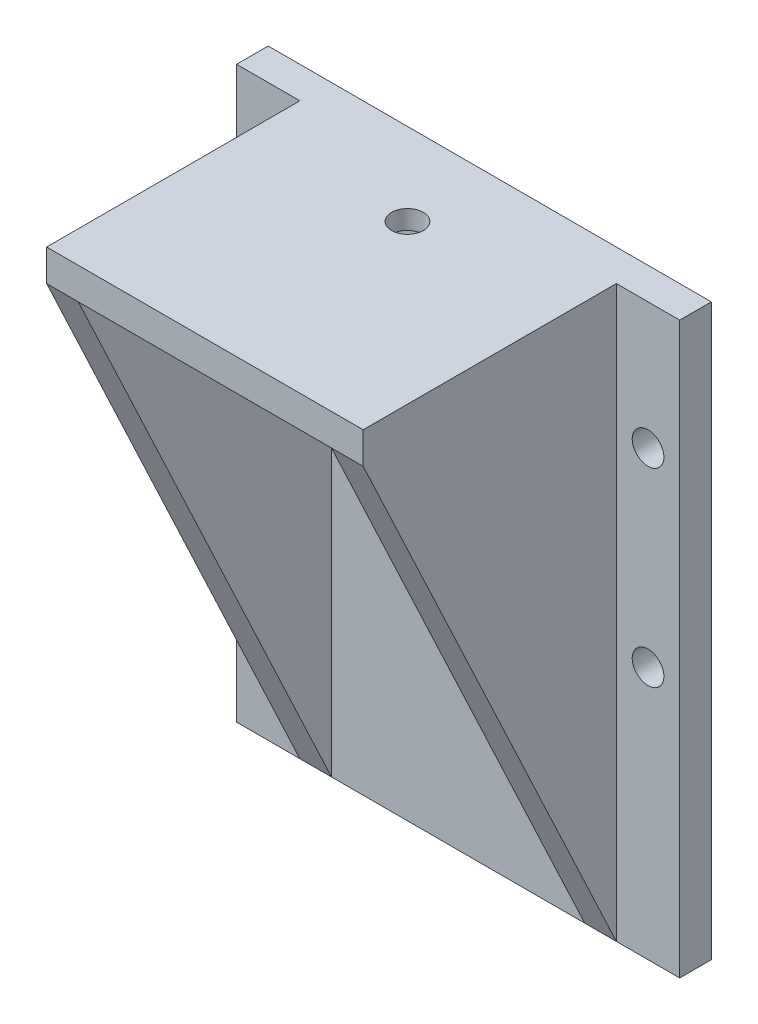
SolidWorks part; units mm, degrees
ref_plane "Plan de face" through (0, 0, 0) normal (0, 0, 1) x (1, 0, 0)
ref_plane "Plan de dessus" through (0, 0, 0) normal (0, 1, 0) x (1, 0, 0)
ref_plane "Plan de droite" through (0, 0, 0) normal (1, 0, 0) x (0, 0, -1)
sketch "Esquisse1" plane through (0, 0, 0) normal (0, 0, 1) x (1, 0, 0)
  line L1 (-46.7149, 53.2769) -> (23.2851, 53.2769)
  line L2 (-46.7149, 53.2769) -> (-46.7149, -36.7231)
  line L3 (-46.7149, -36.7231) -> (23.2851, -36.7231)
  line L4 (23.2851, 53.2769) -> (23.2851, -36.7231)
  dimension "D1" = 90
  dimension "D2" = 70
extrude "Boss.-Extru.1" add sketch "Esquisse1" along normal blind 5
sketch "Esquisse3" plane through (0, 0, 5) normal (0, 0, 1) x (1, 0, 0)
  line L0 (-36.7149, -36.7231) -> (-36.7149, 53.2769)
  line L1 (-46.7149, -36.7231) -> (23.2851, -36.7231) construction
  line L2 (23.2851, 53.2769) -> (-46.7149, 53.2769) construction
  line L3 (-36.7149, 53.2769) -> (13.2851, 53.2769)
  line L4 (13.2851, 53.2769) -> (13.2851, -36.7231)
  line L5 (13.2851, -36.7231) -> (8.2851, -36.7231)
  line L6 (8.2851, -36.7231) -> (8.2851, 48.2769)
  line L7 (8.2851, 48.2769) -> (-31.7149, 48.2769)
  line L8 (-31.7149, 48.2769) -> (-31.7149, -36.7231)
  line L9 (-31.7149, -36.7231) -> (-36.7149, -36.7231)
  line L10 (-46.7149, 53.2769) -> (-46.7149, -36.7231) construction
  line L11 (23.2851, -36.7231) -> (23.2851, 53.2769) construction
  dimension "D1" = 5
  dimension "D2" = 10
  dimension "D3" = 10
  dimension "D4" = 5
  dimension "D5" = 5
extrude "Boss.-Extru.2" add sketch "Esquisse3" along normal blind 40
sketch "Esquisse4" plane through (-36.7149, 0, 0) normal (-1, 0, 0) x (0, 0, 1)
  line L0 (45, 48.2769) -> (5, -36.7231)
  line L1 (45, 53.2769) -> (45, -36.7231) construction
  line L2 (45, -36.7231) -> (5, -36.7231) construction
  line L3 (5, -36.7231) -> (45, -36.7231)
  line L4 (45, -36.7231) -> (45, 48.2769)
  dimension "D1" = 5
extrude "Enlèv. mat.-Extru.1" cut sketch "Esquisse4" against normal up to surface (50 mm away) up to face at (13.2851, -2.9731, 35)
sketch "Esquisse5" plane through (0, 0, 5) normal (0, 0, 1) x (1, 0, 0)
  line L0 (-46.7149, 53.2769) -> (-46.7149, -36.7231) construction
  line L1 (-36.7149, 53.2769) -> (-46.7149, 53.2769) construction
  line L3 (23.2851, -36.7231) -> (23.2851, 53.2769) construction
  line L4 (23.2851, 53.2769) -> (13.2851, 53.2769) construction
  circle A0 centre (-41.7149, 33.2769) radius 2.5
  circle A1 centre (-41.7149, 3.2769) radius 2.5
  circle A2 centre (18.2851, 3.2769) radius 2.5
  circle A3 centre (18.2851, 33.2769) radius 2.5
  dimension "D1" = 5
  dimension "D4" = 5
  dimension "D7" = 5
  dimension "D9" = 5
  dimension "D2" = 5
  dimension "D3" = 20
  dimension "D5" = 5
  dimension "D6" = 20
  dimension "D8" = 5
  dimension "D10" = 30
  dimension "D11" = 30
extrude "Enlèv. mat.-Extru.2" cut sketch "Esquisse5" against normal up to surface (5 mm away) up to face at (-11.7149, 8.2769, 0)
sketch "Esquisse6" plane through (0, 48.2769, 0) normal (0, -1, 0) x (1, 0, 0)
  line L0 (-31.7149, 45) -> (8.2851, 45) construction
  line L3 (-31.7149, 45) -> (-31.7149, 5) construction
  circle A0 centre (-11.7149, 25) radius 19
  dimension "D1" = 38
  dimension "D2" = 20
  dimension "D3" = 20
extrude "Enlèv. mat.-Extru.3" cut sketch "Esquisse6" against normal blind 2
sketch "Esquisse7" plane through (0, 50.2769, 0) normal (0, -1, 0) x (1, 0, 0)
  line L0 (13.2851, 45) -> (-36.7149, 45) construction
  line L1 (-31.7149, 45) -> (-31.7149, 5) construction
  circle A0 centre (-11.7149, 13) radius 2.5
  point P2 (-11.7149, 45)
  dimension "D3" = 5
  dimension "D1" = 32
  dimension "D2" = 20
extrude "Enlèv. mat.-Extru.4" cut sketch "Esquisse7" against normal up to surface (3 mm away) up to face at (-10.4649, 53.2769, 18.75)
